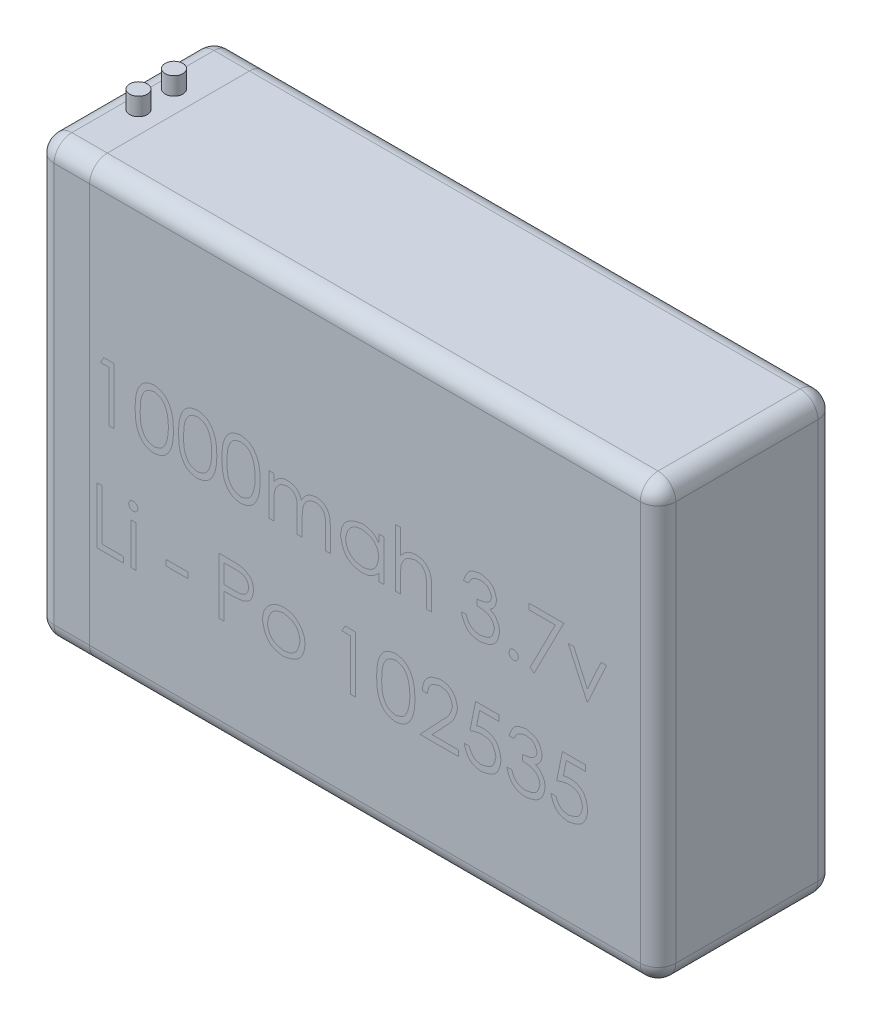
SolidWorks part; units mm, degrees
ref_plane "Front Plane" through (0, 0, 0) normal (0, 0, 1) x (1, 0, 0)
ref_plane "Top Plane" through (0, 0, 0) normal (0, 1, 0) x (1, 0, 0)
ref_plane "Right Plane" through (0, 0, 0) normal (1, 0, 0) x (0, 0, -1)
sketch "Sketch1" plane through (0, 0, 0) normal (0, 0, 1) x (1, 0, 0)
  line L1 (-17.5, -12.25) -> (17.5, -12.25)
  line L2 (-17.5, -12.25) -> (-17.5, 12.25)
  line L3 (-17.5, 12.25) -> (17.5, 12.25)
  line L4 (17.5, -12.25) -> (17.5, 12.25)
  line L5 (0, 12.25) -> (0, -12.25) construction
  line L6 (-17.5, 0) -> (17.5, 0) construction
  point P0 (0, 0)
  dimension "D1" = 35
  dimension "D2" = 24.5
extrude "Boss-Extrude1" add sketch "Sketch1" along normal mid plane 10
fillet "Fillet1" radius 1 12 edges at (17.5, 12.25, 0) (-17.5, 12.25, 0) (-17.5, -12.25, 0) (17.5, -12.25, 0) (0, -12.25, 5) (-17.5, 0, 5) (0, 12.25, 5) (17.5, 0, 5) (0, -12.25, -5) (-17.5, 0, -5) (0, 12.25, -5) (17.5, 0, -5)
sketch "Sketch2" plane through (0, 0, 0) normal (0, 1, 0) x (1, 0, 0)
  line L1 (-24.5027, 8.041) -> (-14.5027, 8.041)
  line L2 (-24.5027, 8.041) -> (-24.5027, -8.1401)
  line L3 (-24.5027, -8.1401) -> (-14.5027, -8.1401)
  line L4 (-14.5027, 8.041) -> (-14.5027, -8.1401)
  dimension "D1" = 10
split line "Split Line1"
sketch "Sketch3" plane through (0, 12.25, 0) normal (0, 1, 0) x (1, 0, 0)
  line L0 (-16.5, 0) -> (-21.2148, 0) construction
  line L1 (-16.5, 4) -> (-16.5, -4) construction
  circle A0 centre (-15.75, 1) radius 0.5
  circle A2 centre (-15.75, -1) radius 0.5
  dimension "D1" = 0.75
  dimension "D3" = 1
  dimension "D2" = 1
extrude "Boss-Extrude2" add sketch "Sketch3" along normal blind 1
sketch "Sketch5" plane through (0, 0, 5) normal (0, 0, 1) x (1, 0, 0)
  line L0 (-14.5027, 0) -> (16.5, 0) construction
  line L1 (-14.5027, -11.25) -> (-14.5027, 11.25) construction
  line L2 (16.5, -11.25) -> (16.5, 11.25) construction
  text T0 "1000mah 3.7v\r\nLi - Po 102535"
  dimension "D1" = 14.2977
wrap "Wrap1" sketch "Sketch5" wrap type scribe source sketch "Sketch5" face at (0.9986, 0, 5)
